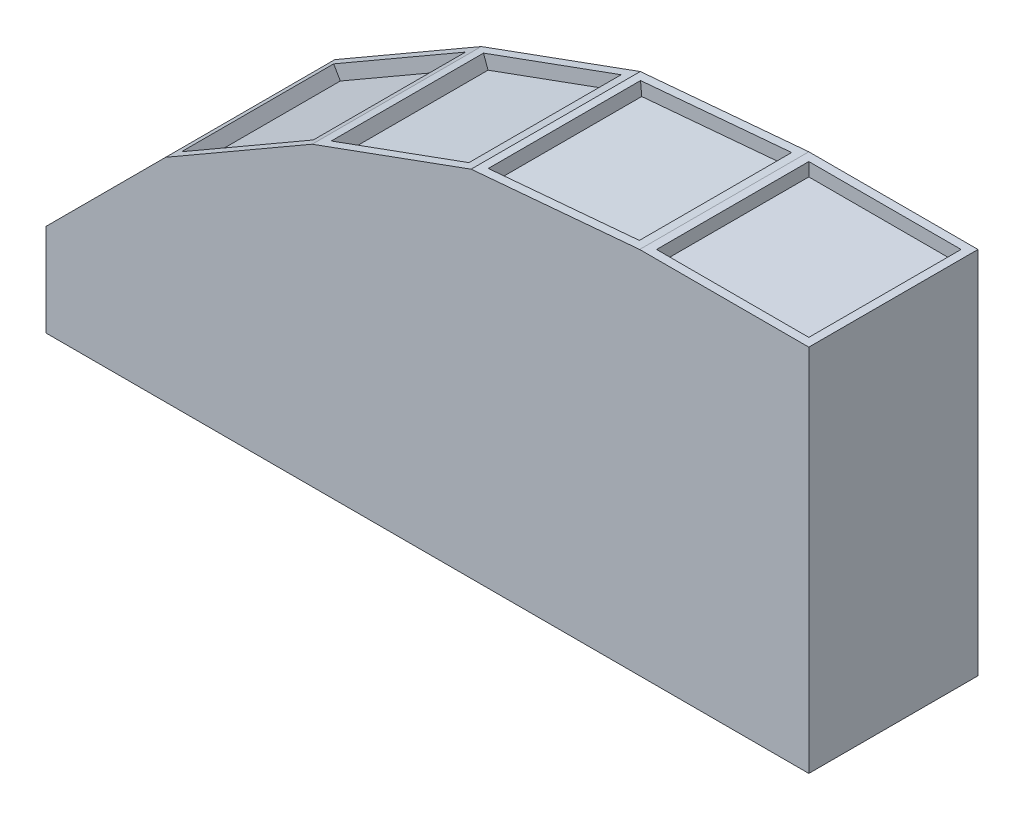
SolidWorks part; units mm, degrees
other "Markup1"
sketch "Sketch34" plane through (-281.715, -69.8831, -95.2498) normal (-0.9907, 0.0223, -0.134) x (-0.0947, 0.5934, 0.7993)
ref_plane "Front Plane" through (0, 0, 0) normal (0, 0, 1) x (1, 0, 0)
ref_plane "Top Plane" through (0, 0, 0) normal (0, 1, 0) x (1, 0, 0)
ref_plane "Right Plane" through (0, 0, 0) normal (1, 0, 0) x (0, 0, -1)
sketch "Sketch1" plane through (0, 0, 0) normal (0, 1, 0) x (1, 0, 0)
  line L1 (0, 0) -> (127, 0)
  line L2 (0, 0) -> (0, 127)
  line L3 (0, 127) -> (127, 127)
  line L4 (127, 0) -> (127, 127)
  line L5 (6.35, 120.65) -> (120.65, 120.65)
  line L6 (6.35, 120.65) -> (6.35, 6.35)
  line L7 (6.35, 6.35) -> (120.65, 6.35)
  line L8 (120.65, 120.65) -> (120.65, 6.35)
  dimension "D1" = 114.3
  dimension "D2" = 114.3
  dimension "D3" = 6.35
  dimension "D4" = 6.35
  dimension "D5" = 6.35
  dimension "D6" = 6.35
extrude "Boss-Extrude1" add sketch "Sketch1" along normal blind 10
ref_plane "Plane1" through (-0.8682, 9.924, 0) normal (-0.0872, 0.9962, 0) x (0, 0, 1)
sketch "Sketch18" plane through (-0.8682, 9.924, 0) normal (-0.0872, 0.9962, 0) x (0, 0, 1)
  line L1 (-127, 0.8716) -> (0, 0.8716)
  line L2 (-127, 0.8716) -> (-127, -126.1284)
  line L3 (-127, -126.1284) -> (0, -126.1284)
  line L4 (0, 0.8716) -> (0, -126.1284)
  dimension "D1" = 127
  dimension "D2" = 127
extrude "Boss-Extrude17" add sketch "Sketch18" against normal blind 10
ref_plane "Plane8" through (-14.4561, 39.7179, 0) normal (-0.342, 0.9397, 0) x (0, 0, 1)
sketch "Sketch20" plane through (-14.4561, 39.7179, 0) normal (-0.342, 0.9397, 0) x (0, 0, 1)
  line L1 (-127, -119.2524) -> (0, -119.2524)
  line L2 (-127, -119.2524) -> (-127, -246.2524)
  line L3 (-127, -246.2524) -> (0, -246.2524)
  line L4 (0, -119.2524) -> (0, -246.2524)
  dimension "D1" = 127
  dimension "D2" = 127
extrude "Boss-Extrude19" add sketch "Sketch20" against normal blind 10
sketch "Sketch21" plane through (-0.8682, 9.924, 0) normal (-0.0872, 0.9962, 0) x (0.9962, 0.0872, 0)
  line L0 (121.0624, 120.65) -> (7.1974, 120.65) construction
  line L1 (-119.561, 120.65) -> (-5.6959, 120.65)
  line L2 (-119.561, 120.65) -> (-119.561, 6.35)
  line L3 (-119.561, 6.35) -> (-5.6959, 6.35)
  line L4 (-5.6959, 120.65) -> (-5.6959, 6.35)
  line L5 (7.1974, 120.65) -> (7.1974, 6.35) construction
  line L6 (0.8716, 127) -> (-126.1284, 127) construction
  line L7 (-126.1284, 127) -> (-126.1284, 0) construction
  point P10 (-62.6284, 127)
  point P11 (-62.6284, 120.65)
  point P14 (-126.1284, 63.5)
  point P15 (-119.561, 63.5)
extrude "Cut-Extrude1" cut sketch "Sketch21" against normal blind 10
sketch "Sketch22" plane through (-14.4561, 39.7179, 0) normal (-0.342, 0.9397, 0) x (0.9397, 0.342, 0)
  line L0 (-246.2524, 127) -> (-246.2524, 0) construction
  line L1 (-237.745, 120.65) -> (-127.7598, 120.65)
  line L2 (-237.745, 120.65) -> (-237.745, 6.35)
  line L3 (-237.745, 6.35) -> (-127.7598, 6.35)
  line L4 (-127.7598, 120.65) -> (-127.7598, 6.35)
  line L5 (-119.2524, 127) -> (-246.2524, 127) construction
  line L6 (-2.9235, 120.65) -> (-112.9087, 120.65) construction
  line L7 (-112.9087, 120.65) -> (-112.9087, 6.35) construction
  point P6 (-246.2524, 63.5)
  point P7 (-237.745, 63.5)
  point P10 (-182.7524, 127)
  point P11 (-182.7524, 120.65)
extrude "Cut-Extrude2" cut sketch "Sketch22" against normal blind 10
sketch "Sketch23" plane through (0, 0, 0) normal (0, -1, 0) x (1, 0, 0)
  line L1 (0, 0) -> (127, 0)
  line L2 (0, 0) -> (0, -127)
  line L3 (0, -127) -> (127, -127)
  line L4 (127, 0) -> (127, -127)
extrude "Boss-Extrude21" add sketch "Sketch23" along normal blind 10
sketch "Sketch24" plane through (0.0033, -0.0379, 0) normal (0.0872, -0.9962, 0) x (0.9962, 0.0872, 0)
  line L0 (-124.8119, 0) -> (-0.0033, 0) construction
  line L1 (-124.8119, 0) -> (2.1881, 0)
  line L2 (-124.8119, 0) -> (-124.8119, -127)
  line L3 (-124.8119, -127) -> (2.1881, -127)
  line L4 (2.1881, 0) -> (2.1881, -127)
  line L5 (-0.0033, -127) -> (-124.8119, -127) construction
  dimension "D1" = 127
extrude "Boss-Extrude24" add sketch "Sketch24" along normal blind 10
sketch "Sketch25" plane through (-11.0359, 30.321, 0) normal (0.342, -0.9397, 0) x (0.9397, 0.342, 0)
  line L0 (-246.2524, -127) -> (-246.2524, 0) construction
  line L1 (-246.2524, 0) -> (-119.2524, 0)
  line L2 (-246.2524, 0) -> (-246.2524, -127)
  line L3 (-246.2524, -127) -> (-119.2524, -127)
  line L4 (-119.2524, 0) -> (-119.2524, -127)
  dimension "D1" = 127
  dimension "D2" = 127
extrude "Boss-Extrude25" add sketch "Sketch25" along normal blind 10
ref_plane "Plane9" through (-42.193, 73.0805, 0) normal (-0.5, 0.866, 0) x (0, 0, 1)
sketch "Sketch26" plane through (-42.193, 73.0805, 0) normal (-0.5, 0.866, 0) x (0, 0, 1)
  line L1 (-127, -235.1717) -> (0, -235.1717)
  line L2 (-127, -235.1717) -> (-127, -362.1717)
  line L3 (-127, -362.1717) -> (0, -362.1717)
  line L4 (0, -235.1717) -> (0, -362.1717)
  dimension "D1" = 127
  dimension "D2" = 127
extrude "Boss-Extrude26" add sketch "Sketch26" against normal blind 10
sketch "Sketch27" plane through (-42.193, 73.0805, 0) normal (-0.5, 0.866, 0) x (0.866, 0.5, 0)
  line L0 (-235.1717, 127) -> (-362.1717, 127) construction
  line L1 (-355.8217, 120.65) -> (-241.5217, 120.65)
  line L2 (-355.8217, 120.65) -> (-355.8217, 6.35)
  line L3 (-355.8217, 6.35) -> (-241.5217, 6.35)
  line L4 (-241.5217, 120.65) -> (-241.5217, 6.35)
  line L5 (-362.1717, 127) -> (-362.1717, 0) construction
  point P6 (-298.6717, 127)
  point P7 (-298.6717, 120.65)
  point P10 (-362.1717, 63.5)
  point P11 (-355.8217, 63.5)
  dimension "D1" = 114.3
  dimension "D2" = 114.3
extrude "Cut-Extrude3" cut sketch "Sketch27" against normal blind 10
sketch "Sketch28" plane through (-37.193, 64.4202, 0) normal (0.5, -0.866, 0) x (0.866, 0.5, 0)
  line L1 (-362.1717, 0) -> (-235.1717, 0)
  line L2 (-362.1717, 0) -> (-362.1717, -127)
  line L3 (-362.1717, -127) -> (-235.1717, -127)
  line L4 (-235.1717, 0) -> (-235.1717, -127)
  dimension "D1" = 127
  dimension "D2" = 127
extrude "Boss-Extrude27" add sketch "Sketch28" along normal blind 10
ref_plane "Plane10" through (-123.9188, 123.9188, 0) normal (-0.7071, 0.7071, 0) x (0, 0, 1)
sketch "Sketch29" plane through (-123.9188, 123.9188, 0) normal (-0.7071, 0.7071, 0) x (0, 0, 1)
  line L1 (-127, -327.9902) -> (0, -327.9902)
  line L2 (-127, -327.9902) -> (-127, -454.9902)
  line L3 (-127, -454.9902) -> (0, -454.9902)
  line L4 (0, -327.9902) -> (0, -454.9902)
  dimension "D1" = 127
  dimension "D2" = 127
extrude "Boss-Extrude28" add sketch "Sketch29" against normal blind 10
sketch "Sketch30" plane through (-123.9188, 123.9188, 0) normal (-0.7071, 0.7071, 0) x (0, 0, 1)
  line L0 (-127, -454.9902) -> (0, -454.9902) construction
  line L1 (-120.65, -334.3402) -> (-6.35, -334.3402)
  line L2 (-120.65, -334.3402) -> (-120.65, -448.6402)
  line L3 (-120.65, -448.6402) -> (-6.35, -448.6402)
  line L4 (-6.35, -334.3402) -> (-6.35, -448.6402)
  line L5 (-127, -327.9902) -> (-127, -454.9902) construction
  point P6 (-63.5, -454.9902)
  point P7 (-63.5, -448.6402)
  point P10 (-127, -391.4902)
  point P11 (-120.65, -391.4902)
  dimension "D1" = 114.3
  dimension "D2" = 114.3
extrude "Cut-Extrude4" cut sketch "Sketch30" against normal blind 10
sketch "Sketch31" plane through (-116.8477, 116.8477, 0) normal (0.7071, -0.7071, 0) x (0, 0, -1)
  line L1 (0, -454.9902) -> (127, -454.9902)
  line L2 (0, -454.9902) -> (0, -327.9902)
  line L3 (0, -327.9902) -> (127, -327.9902)
  line L4 (127, -454.9902) -> (127, -327.9902)
  dimension "D1" = 127
  dimension "D2" = 127
extrude "Boss-Extrude29" add sketch "Sketch31" along normal blind 10
sketch "Sketch32" plane through (0, 0, 0) normal (0, 0, 1) x (1, 0, 0)
  line L1 (127, -241.7679) -> (127, -10)
  line L2 (127, -10) -> (0.8732, -10)
  line L3 (0.8732, -10) -> (-122.1506, -20.7632)
  line L4 (-122.1506, -20.7632) -> (-237.373, -62.7007)
  line L5 (-237.373, -62.7007) -> (-343.5626, -124.0093)
  line L6 (-343.5626, -124.0093) -> (-431.5033, -211.95)
  line L10 (127, -241.7679) -> (127, -267.1679)
  line L11 (127, -267.1679) -> (-445.6455, -267.1679)
  line L12 (-445.6455, -267.1679) -> (-445.6455, -197.8079)
  line L13 (-445.6455, -197.8079) -> (-431.5033, -211.95)
  dimension "D1" = 25.4
extrude "Boss-Extrude30" add sketch "Sketch32" against normal up to surface (127 mm away) up to face at (-171.1316, -64.2342, -127)
sketch "Sketch33" plane through (0, 0, -127) normal (0, 0, -1) x (-1, 0, 0)
  line L0 (-127, 10) -> (-127, -267.1679) construction
  line L1 (-127, 10) -> (0, 10) construction
  line L2 (0, 10) -> (126.5167, -1.0688) construction
  line L3 (126.5167, -1.0688) -> (245.8577, -44.5053) construction
  line L4 (245.8577, -44.5053) -> (355.8429, -108.0053) construction
  line L5 (355.8429, -108.0053) -> (445.6455, -197.8079) construction
  text T0 "0"
  text T1 "5"
  text T2 "15\r\n"
  text T3 "30\r\n"
  text T4 "45\r\n"
  dimension "D1" = 63.5
  dimension "D2" = 12.7
  dimension "D3" = 12.7
  dimension "D4" = 190.5
  dimension "D5" = 12.7
  dimension "D6" = 317.5
  dimension "D7" = 12.7
  dimension "D8" = 419.1
  dimension "D9" = 12.7
  dimension "D10" = 520.7
extrude "Cut-Extrude5" cut sketch "Sketch33" against normal blind 2.54
scale "Scale5" scale about centroid uniform scaling yes scale factor 0.5
